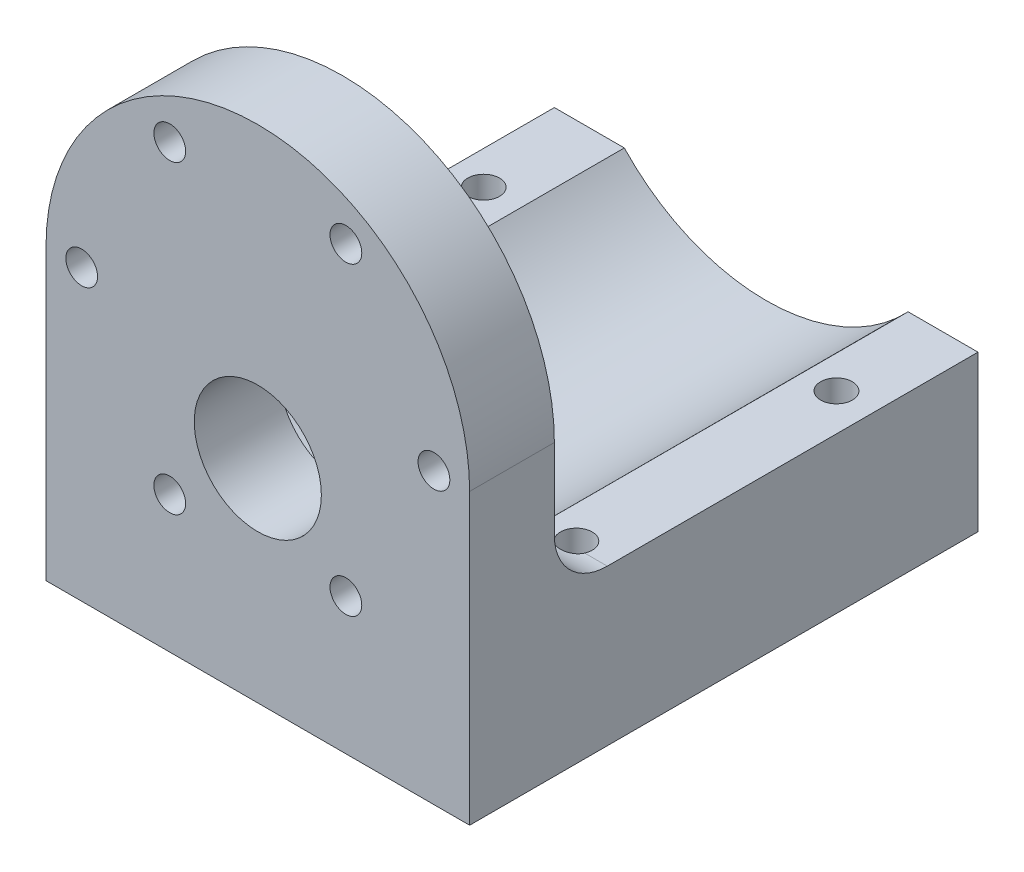
SolidWorks part; units mm, degrees
ref_plane "Спереди" through (0, 0, 0) normal (0, 0, 1) x (1, 0, 0)
ref_plane "Сверху" through (0, 0, 0) normal (0, 1, 0) x (1, 0, 0)
ref_plane "Справа" through (0, 0, 0) normal (1, 0, 0) x (0, 0, -1)
sketch "Эскиз1" plane through (0, 0, 0) normal (0, 0, 1) x (1, 0, 0)
  line L0 (20, 27.3) -> (20, 7.3) construction
  line L1 (0, 0) -> (40, 0)
  line L5 (0, 0) -> (0, 27.3)
  line L6 (40, 27.3) -> (40, 0)
  circle A1 centre (20, 20) radius 6
  circle A2 centre (20, 27.3) radius 16.63 construction
  circle A3 centre (3.37, 27.3) radius 1.5
  circle A4 centre (11.685, 41.702) radius 1.5
  circle A5 centre (28.315, 41.702) radius 1.5
  circle A6 centre (36.63, 27.3) radius 1.5
  circle A7 centre (28.315, 12.898) radius 1.5
  circle A8 centre (11.685, 12.898) radius 1.5
  arc A9 (0, 27.3) -> (40, 27.3) centre (20, 27.3) cw
  circle A10 centre (20, 27.3) radius 18.3 construction
  point P26 (20, 27.3)
  dimension "D1" = 36.6
  dimension "D4" = 12
  dimension "D6" = 33.26
  dimension "D7" = 3
  dimension "D2" = 27.3
  dimension "D3" = 12.7
  dimension "D5" = 20
  dimension "D8" = 6
extrude "Бобышка-Вытянуть2" add sketch "Эскиз1" along normal blind 8 contours L6 L1 L5 A9
extrude "Вырез-Вытянуть2" cut sketch "Эскиз1<11>" along normal through all flip side to cut
sketch "Эскиз1<11>" plane through (0, 0, 0) normal (0, 0, 1) x (1, 0, 0) same geometry as "Эскиз1"
sketch "Эскиз8" plane through (0, 0, 0) normal (0, 0, -1) x (-1, 0, 0)
  line L0 (0, 0) -> (-40, 0) construction
  line L1 (-40, 27.3) -> (-40, 0) construction
  line L2 (-40, 27.3) -> (-38.4, 27.3)
  line L3 (0, 27.3) -> (-1.6, 27.3)
  line L4 (0, 14.6877) -> (-6.6026, 14.6877)
  line L5 (0, 0) -> (0, 27.3) construction
  line L6 (-6.6026, 14.6877) -> (-40, 14.6877) construction
  line L7 (-33.3848, 14.6877) -> (-40, 14.6877)
  circle A0 centre (-20, 27.3) radius 18.4
  line M10 (-40, 27.3) -> (-40, 0)
  line M11 (-40, 0) -> (0, 0)
  line M12 (0, 0) -> (0, 27.3)
  dimension "D2" = 36.8
  dimension "D1" = 27.3
  dimension "D3" = 20
extrude "Бобышка-Вытянуть4" add sketch "Эскиз8" along normal blind 40 contours A0 L7 L4 M10 M11 M12 region at (20, 6.2298, 0)
sketch "Эскиз9" plane through (0, 14.6877, 0) normal (0, 1, 0) x (1, 0, 0)
  circle A0 centre (36.4878, 5.5862) radius 1.5
  circle A1 centre (3.1746, 5.5862) radius 1.5
  circle A2 centre (3.1746, 30.1478) radius 1.5
  circle A3 centre (36.4878, 30.1478) radius 1.5
  dimension "D1" = 3
  dimension "D2" = 3
  dimension "D3" = 3
  dimension "D4" = 3
extrude "Вырез-Вытянуть3" cut sketch "Эскиз9" against normal through all
fillet "Скругление1" radius 5 1 edges at (36.6987, 14.6877, 0)
fillet "Скругление2" radius 5 1 edges at (3.3013, 14.6877, 0)
